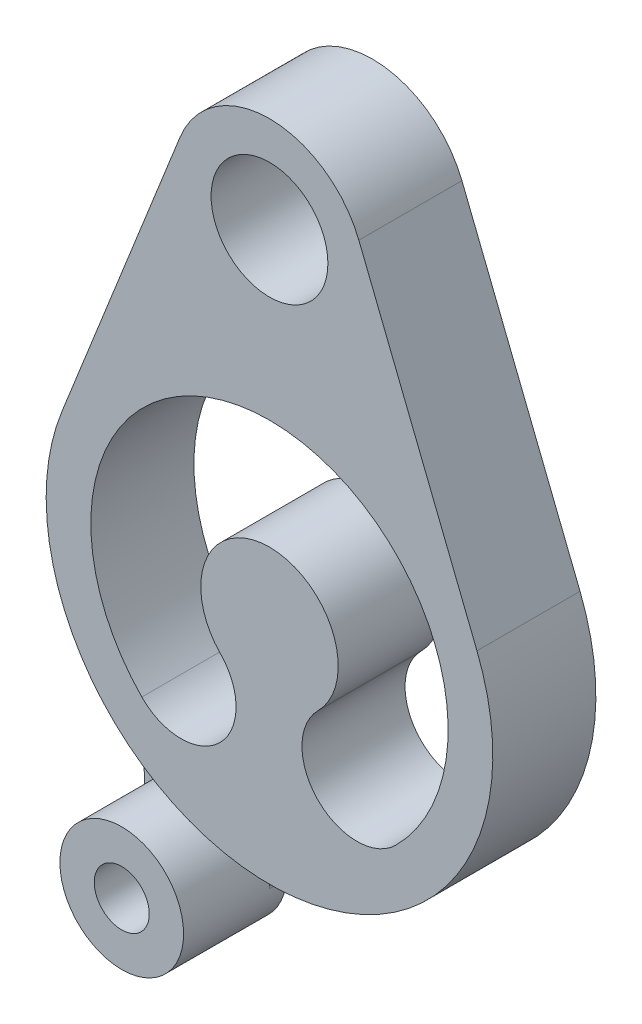
SolidWorks part; units mm, degrees
ref_plane "Front Plane" through (0, 0, 0) normal (0, 0, 1) x (1, 0, 0)
ref_plane "Top Plane" through (0, 0, 0) normal (0, 1, 0) x (1, 0, 0)
ref_plane "Right Plane" through (0, 0, 0) normal (1, 0, 0) x (0, 0, -1)
sketch "Sketch2" plane through (0, 0, 0) normal (0, 0, 1) x (1, 0, 0)
  line L0 (0, -1102.2062) -> (0, -48) construction
  line L1 (0, -100) -> (25.4558, -125.4558) construction
  line L2 (26.0129, 10.36) -> (60.3871, -75.95)
  line L3 (-26.0129, 10.36) -> (-60.3871, -75.95)
  line L4 (0, -35) -> (0, 50000) construction
  line L5 (-65, -100) -> (-61.0176, -190.0008)
  circle A0 centre (0, 0) radius 17
  arc A1 (25.4558, -125.4558) -> (-25.7298, -125.1789) centre (0, -100) ccw construction
  arc A2 (36.7696, -136.7696) -> (-37.1653, -136.3695) centre (0, -100) ccw
  arc A3 (14.1421, -114.1421) -> (-14.2944, -113.9883) centre (0, -100) ccw
  arc A4 (14.1421, -114.1421) -> (36.7696, -136.7696) centre (25.4558, -125.4558) ccw
  arc A5 (-37.1653, -136.3695) -> (-14.2944, -113.9883) centre (-25.7298, -125.1789) ccw
  arc A6 (-60.3871, -75.95) -> (60.3871, -75.95) centre (0, -100) ccw
  arc A7 (26.0129, 10.36) -> (-26.0129, 10.36) centre (0, 0) ccw
  circle A8 centre (-43, -190) radius 18
  circle A9 centre (-43, -190) radius 8
  arc A10 (3.1017, -165.1932) -> (-25, -190) centre (0, -190) ccw
  point P7 (0.1948, -64.0005)
  point P29 (-101.289, -221.9256)
  point P30 (0, 0)
  point P31 (-101.6478, -269.043)
  point P32 (-107.4022, -233.3896)
  point P33 (0, 0)
  point P34 (-61, -190)
  dimension "D1" = 34
  dimension "D2" = 100
  dimension "D3" = 36
  dimension "D5" = 130
  dimension "D6" = 56
  dimension "D7" = 16
  dimension "D8" = 90
  dimension "D9" = 16
  dimension "D10" = 36
  dimension "D4" = 45
  dimension "D11" = 0.1948
  dimension "D12" = 3.1017
  dimension "D16" = 61.0176
extrude "Boss-Extrude1" add sketch "Sketch2" along normal blind 30 contours L2 A7 L3 A6 L5 A0 A5 A2 A4 A3 region at (41.0381, -33.656, 0)
extrude "Boss-Extrude2" add sketch "Sketch2<4>" along normal blind 30 separate body contours A8 A9 region at (-60.4909, -190, 0)
sketch "Sketch2<4>" plane through (0, 0, 0) normal (0, 0, 1) x (1, 0, 0) same geometry as "Sketch2"
sketch "Sketch3" plane through (0, 0, 0) normal (0, 0, 1) x (1, 0, 0)
  line L0 (-64.746, -105.7411) -> (-61, -190)
  circle A0 centre (-43, -190) radius 18 construction
  arc A1 (-64.746, -105.7411) -> (60.3871, -75.95) centre (0, -100) ccw construction
  circle A2 centre (-43, -190) radius 18
  arc A3 (-64.746, -105.7411) -> (2.0304, -164.9683) centre (0, -100) ccw
  arc A4 (2.0304, -164.9683) -> (-25.0372, -191.1562) centre (2.905, -192.9546) ccw
  point P10 (-0.9483, -164.9931)
  point P11 (0, 0)
  dimension "D1" = 28
extrude "Boss-Extrude3" add sketch "Sketch3" along normal blind 5 contours A4 A3 L0 A2 region at (-43.7866, -159.4995, 0)
